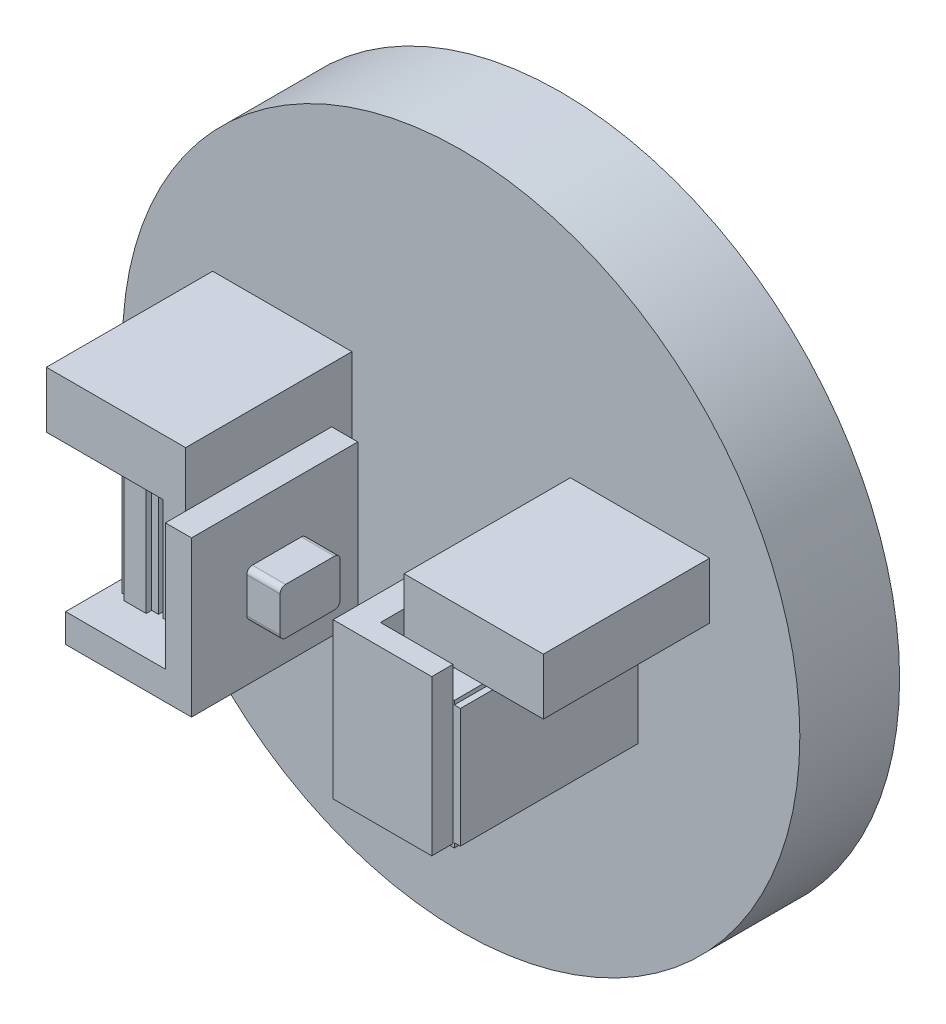
SolidWorks part; units mm, degrees
ref_plane "前视基准面" through (0, 0, 0) normal (0, 0, 1) x (1, 0, 0)
ref_plane "上视基准面" through (0, 0, 0) normal (0, 1, 0) x (1, 0, 0)
ref_plane "右视基准面" through (0, 0, 0) normal (1, 0, 0) x (0, 0, -1)
other "Configuration Table"
sketch "草图1" plane through (0, 0, 0) normal (0, 0, 1) x (1, 0, 0)
  circle A0 centre (0, 0) radius 30.5491
extrude "凸台-拉伸1" add sketch "草图1" along normal blind 9
sketch "草图3" plane through (0, 0, 9) normal (0, 0, 1) x (1, 0, 0)
  line L0 (0, -4.95) -> (0, 4.95) construction
  line L1 (-22.4135, 4.7787) -> (-11.9046, 4.7787)
  line L2 (-22.4135, 4.7787) -> (-22.4135, 9.8521)
  line L3 (-22.4135, 9.8521) -> (-9.8521, 9.8521)
  line L4 (-9.8521, 7.307) -> (-9.8521, 9.8521)
  line L5 (22.4135, 9.8521) -> (9.8521, 9.8521)
  line L6 (9.8521, 7.307) -> (9.8521, 9.8521)
  line L7 (22.4135, 4.7787) -> (11.9046, 4.7787)
  line L8 (22.4135, 4.7787) -> (22.4135, 9.8521)
  line L9 (9.8521, -4.4893) -> (11.9046, -4.4893)
  line L11 (-9.8521, 7.307) -> (-9.8521, -4.4893)
  line L12 (-9.8521, -4.4893) -> (-11.9046, -4.4893)
  line L13 (-11.9046, 4.7787) -> (-11.9046, -4.4893)
  line L14 (11.9046, 4.7787) -> (11.9046, -4.4893)
  line L16 (9.8521, 7.307) -> (9.8521, -4.4893)
extrude "凸台-拉伸2" add sketch "草图3" along normal blind 15
ref_plane "基准面1" through (0, 0, 15) normal (0, 0, 1) x (1, 0, 0)
sketch "草图8" plane through (0, 0, 0) normal (0, 1, 0) x (1, 0, 0)
  line L0 (0, -13.2) -> (0, 13.2) construction
  line L1 (-8.7419, -11.9359) -> (-6.388, -11.9359)
  line L2 (-8.7419, -11.9359) -> (-8.7419, -26.9359)
  line L3 (-8.7419, -26.9359) -> (-6.388, -26.9359)
  line L4 (-6.388, -11.9359) -> (-6.388, -26.9359)
  line L5 (6.388, -11.9359) -> (6.388, -26.9359)
  line L6 (8.7419, -26.9359) -> (6.388, -26.9359)
  line L7 (8.7419, -11.9359) -> (8.7419, -26.9359)
  line L8 (8.7419, -11.9359) -> (6.388, -11.9359)
extrude "凸台-拉伸3" add sketch "草图8" against normal blind 8 separate body
sketch "草图12" plane through (0, 0, 0) normal (0, 1, 0) x (1, 0, 0)
  line L1 (-6.388, -26.9359) -> (-8.7419, -26.9359)
  line L2 (-6.388, -26.9359) -> (-6.388, -11.9359)
  line L3 (-6.388, -11.9359) -> (-8.7419, -11.9359)
  line L4 (-8.7419, -26.9359) -> (-8.7419, -11.9359)
  line L5 (8.7419, -11.9359) -> (6.388, -11.9359)
  line L6 (8.7419, -11.9359) -> (8.7419, -26.9359)
  line L7 (8.7419, -26.9359) -> (6.388, -26.9359)
  line L8 (6.388, -11.9359) -> (6.388, -26.9359)
extrude "凸台-拉伸5" add sketch "草图12" along normal blind 6
sketch "草图14" plane through (0, 0, 0) normal (1, 0, 0) x (0, 0, -1)
  line L1 (-26.9359, -5.4337) -> (-11.9359, -5.4337)
  line L2 (-26.9359, -5.4337) -> (-26.9359, -8)
  line L3 (-26.9359, -8) -> (-11.9359, -8)
  line L4 (-11.9359, -5.4337) -> (-11.9359, -8)
extrude "凸台-拉伸7" add sketch "草图14" against normal blind 9 from surface starting at face at (-8.7419, -1, 19.4359)
sketch "草图15" plane through (0, 0, 0) normal (0, 1, 0) x (1, 0, 0)
  line L1 (8.7419, -26.9359) -> (15.283, -26.9359)
  line L2 (8.7419, -26.9359) -> (8.7419, -25.0205)
  line L3 (8.7419, -25.0205) -> (15.283, -25.0205)
  line L4 (15.283, -26.9359) -> (15.283, -25.0205)
extrude "凸台-拉伸8" add sketch "草图15" along direction (0, 1, 0) on the side of the normal up to surface (6 mm away) up to face at (7.5649, 6, 19.4359)
extrude "凸台-拉伸9" add sketch "草图15<2>" against normal up to surface (8 mm away) up to face at (7.5649, -8, 19.4359)
sketch "草图15<2>" plane through (0, 0, 0) normal (0, 1, 0) x (1, 0, 0) same geometry as "草图15"
sketch "草图16" plane through (0, 0, 9) normal (0, 0, 1) x (1, 0, 0)
  line L0 (15.4021, -7.866) -> (15.9545, -7.866)
  line L1 (12.5686, -7.866) -> (12.8526, -7.866)
  line L2 (12.5686, -7.866) -> (12.5686, 2.8918)
  line L3 (12.5686, 2.8918) -> (12.8526, 2.8918)
  line L4 (15.9545, -7.866) -> (15.9545, 2.8918)
  line L6 (15.4021, 2.8918) -> (15.4021, 3.2446)
  line L7 (15.4021, 3.2446) -> (12.8526, 3.2446)
  line L8 (12.8526, 2.8918) -> (12.8526, 3.2446)
  line L10 (15.4021, -7.866) -> (15.4021, -8.2861)
  line L11 (15.4021, -8.2861) -> (12.8526, -8.2861)
  line L12 (12.8526, -7.866) -> (12.8526, -8.2861)
  line L13 (15.4021, 2.8918) -> (15.9545, 2.8918)
extrude "凸台-拉伸10" add sketch "草图16" along normal up to surface (16.0205 mm away) up to face at (12.0125, -1, 25.0205)
sketch "草图18" plane through (0, 4.7787, 0) normal (0, -1, 0) x (1, 0, 0)
  line L0 (-15.9809, 13.4001) -> (-16.6089, 13.4001)
  line L5 (-13.329, 13.4001) -> (-13.9571, 13.4001)
  line L6 (-13.329, 13.4001) -> (-13.329, 22.9607)
  line L7 (-13.329, 22.9607) -> (-13.9571, 22.9607)
  line L8 (-16.6089, 13.4001) -> (-16.6089, 22.9607)
  line L10 (-15.9809, 22.9607) -> (-15.9809, 23.4492)
  line L11 (-15.9809, 23.4492) -> (-13.9571, 23.4492)
  line L12 (-13.9571, 22.9607) -> (-13.9571, 23.4492)
  line L14 (-15.9809, 13.4001) -> (-15.9809, 13.1082)
  line L15 (-15.9809, 13.1082) -> (-13.9571, 13.1082)
  line L16 (-13.9571, 13.4001) -> (-13.9571, 13.1082)
  line L17 (-15.9809, 22.9607) -> (-16.6089, 22.9607)
extrude "凸台-拉伸11" add sketch "草图18" along normal up to surface (12.7787 mm away) up to face at (-12.0649, -8, 19.4359)
sketch "草图19" plane through (-6.388, 0, 0) normal (1, 0, 0) x (0, 0, -1)
  line L1 (-21.9447, -3.0725) -> (-16.5375, -3.0725)
  line L2 (-21.9447, -3.0725) -> (-21.9447, 1.1252)
  line L3 (-21.9447, 1.1252) -> (-16.5375, 1.1252)
  line L4 (-16.5375, -3.0725) -> (-16.5375, 1.1252)
extrude "凸台-拉伸12" add sketch "草图19" along normal blind 3
fillet "圆角1" radius 0.5 4 edges at (-4.888, -3.0725, 16.5375) (-4.888, 1.1252, 16.5375) (-4.888, -3.0725, 21.9447) (-4.888, 1.1252, 21.9447)
mirror "镜向4" about plane through (0, 0, 0) normal (1, 0, 0) of "凸台-拉伸12", "圆角1"
